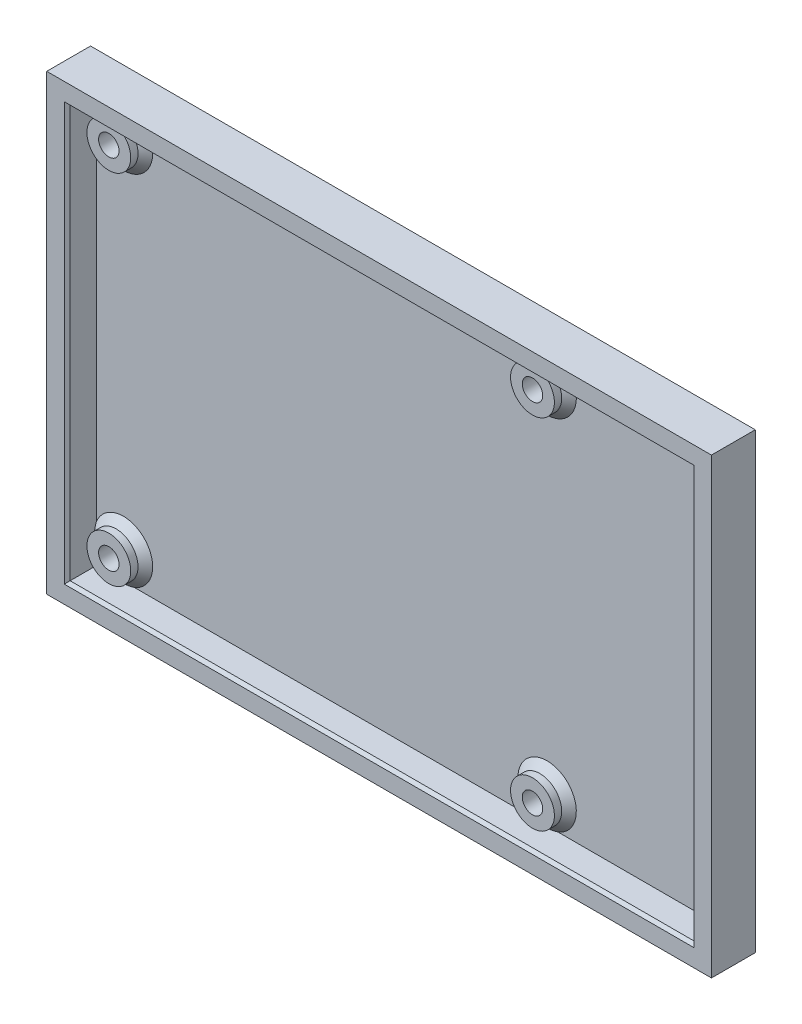
SolidWorks part; units mm, degrees
ref_plane "前视基准面" through (0, 0, 0) normal (0, 0, 1) x (1, 0, 0)
ref_plane "上视基准面" through (0, 0, 0) normal (0, 1, 0) x (1, 0, 0)
ref_plane "右视基准面" through (0, 0, 0) normal (1, 0, 0) x (0, 0, -1)
other "Configuration Table"
sketch "Sketch1" plane through (0, 0, 0) normal (0, 0, 1) x (1, 0, 0)
  line L1 (-45.5, -31) -> (45.5, -31)
  line L2 (-45.5, -31) -> (-45.5, 31)
  line L3 (-45.5, 31) -> (45.5, 31)
  line L4 (45.5, -31) -> (45.5, 31)
  line L5 (-45.5, -31) -> (45.5, 31) construction
  line L6 (-45.5, 31) -> (45.5, -31) construction
  point P0 (0, 0)
  dimension "D1" = 62
  dimension "D2" = 91
extrude "Boss-Extrude1" add sketch "Sketch1" along normal blind 6
sketch "Sketch2" plane through (0, 0, 6) normal (0, 0, 1) x (1, 0, 0)
  line L1 (-42.7, -28.2) -> (42.7, -28.2)
  line L2 (-42.7, -28.2) -> (-42.7, 28.2)
  line L3 (-42.7, 28.2) -> (42.7, 28.2)
  line L4 (42.7, -28.2) -> (42.7, 28.2)
  line L5 (-42.7, -28.2) -> (42.7, 28.2) construction
  line L6 (-42.7, 28.2) -> (42.7, -28.2) construction
  point P0 (0, 0)
  dimension "D1" = 85.4
  dimension "D2" = 56.4
extrude "Cut-Extrude1" cut sketch "Sketch2" against normal blind 4
sketch "Sketch3" plane through (0, 0, 2) normal (0, 0, 1) x (1, 0, 0)
  line L0 (42.7, 28.2) -> (-42.7, 28.2) construction
  line L1 (-42.7, 28.2) -> (-42.7, -28.2) construction
  circle A0 centre (-39, 24.5) radius 3
  circle A1 centre (-39, 24.5) radius 1.4
  dimension "D1" = 2.8
  dimension "D2" = 6
  dimension "D3" = 3.7
  dimension "D4" = 3.7
extrude "Boss-Extrude2" add sketch "Sketch3" along normal blind 2
chamfer "Chamfer1" distance 1 angle 45 1 edges at (-42, 24.5, 2)
chamfer "Chamfer2" distance 0.4 angle 45 4 edges at (0, -28.2, 6) (42.7, 0, 6) (-42.7, 0, 6) (0, 28.2, 6)
pattern_linear "LPattern1" count 2 spacing 58 along (1, 0, 0) count 2 spacing 49 along (0, -1, 0) of "Boss-Extrude2", "Chamfer1"
